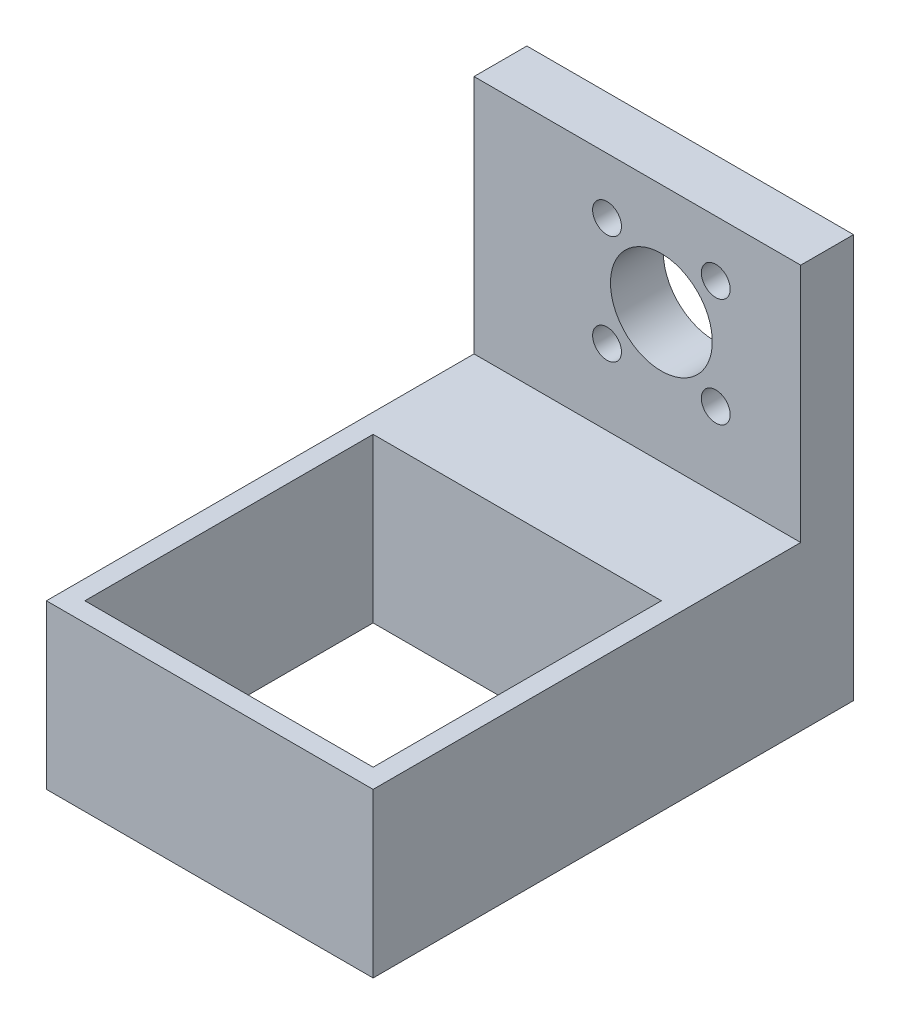
SolidWorks part; units mm, degrees
ref_plane "Płaszczyzna przednia" through (0, 0, 0) normal (0, 0, 1) x (1, 0, 0)
ref_plane "Płaszczyzna górna" through (0, 0, 0) normal (0, 1, 0) x (1, 0, 0)
ref_plane "Płaszczyzna prawa" through (0, 0, 0) normal (1, 0, 0) x (0, 0, -1)
sketch "Szkic1" plane through (0, 0, 0) normal (0, 1, 0) x (1, 0, 0)
  line L1 (-17, 25) -> (17, 25)
  line L2 (-17, 25) -> (-17, -25)
  line L3 (-17, -25) -> (17, -25)
  line L4 (17, 25) -> (17, -25)
  line L5 (-17, 25) -> (17, -25) construction
  line L6 (-17, -25) -> (17, 25) construction
  point P0 (0, 0)
  dimension "D1" = 34
  dimension "D2" = 50
extrude "Dodanie-wyciągnięcie1" add sketch "Szkic1" along normal blind 17
sketch "Szkic2" plane through (0, 17, 0) normal (0, 1, 0) x (1, 0, 0)
  line L0 (0, 25) -> (0, -25) construction
  line L1 (17, 25) -> (-17, 25) construction
  line L2 (-17, -25) -> (17, -25) construction
  line L3 (-17, 25) -> (-17, -25) construction
  line L4 (15, 7) -> (-15, 7)
  line L5 (15, 7) -> (15, -23)
  line L6 (15, -23) -> (-15, -23)
  line L7 (-15, 7) -> (-15, -23)
  line L8 (15, 7) -> (-15, -23) construction
  line L9 (15, -23) -> (-15, 7) construction
  point P6 (0, -8)
  dimension "D1" = 2
  dimension "D2" = 2
  dimension "D3" = 30
extrude "Wytnij-wyciągnięcie1" cut sketch "Szkic2" against normal blind 20
sketch "Szkic3" plane through (0, 17, 0) normal (0, 1, 0) x (1, 0, 0)
  line L0 (17, -25) -> (17, 25) construction
  line L1 (17, 25) -> (-17, 25)
  line L2 (17, 25) -> (17, 19.5)
  line L3 (17, 19.5) -> (-17, 19.5)
  line L4 (-17, 25) -> (-17, 19.5)
  line L5 (17, 25) -> (-17, 25) construction
  line L6 (-17, 25) -> (-17, -25) construction
  line L7 (-17, -25) -> (17, -25) construction
  dimension "D1" = 44.5
extrude "Dodanie-wyciągnięcie2" add sketch "Szkic3" along normal blind 25
sketch "Szkic4" plane through (0, 0, -25) normal (0, 0, -1) x (-1, 0, 0)
  line L0 (-17, 0) -> (17, 0) construction
  line L1 (-2.5, 30.5) -> (-8.1569, 36.1569) construction
  line L2 (-2.5, 30.5) -> (-2.5, 38.5) construction
  line L3 (-17, 42) -> (17, 42) construction
  circle A0 centre (3.1569, 36.1569) radius 1.5
  circle A1 centre (-2.5, 30.5) radius 5.3
  circle A2 centre (-2.5, 30.5) radius 8
  circle A3 centre (-8.1569, 36.1569) radius 1.5
  circle A4 centre (-2.5, 30.5) radius 8
  circle A5 centre (3.1569, 24.8431) radius 1.5
  circle A6 centre (-2.5, 30.5) radius 8
  circle A7 centre (-8.1569, 24.8431) radius 1.5
  circle A8 centre (-2.5, 30.5) radius 8
  point P4 (0, 0)
  point P5 (0, 0)
  point P21 (-2.5, 30.5)
  dimension "D2" = 11.5
  dimension "D3" = 10.6
  dimension "D4" = 16
  dimension "D5" = 3
  dimension "D6" = 45
  dimension "2,5" = 2.5
  dimension "D7" = 4
extrude "Wytnij-wyciągnięcie2" cut sketch "Szkic4" against normal blind 25 contours A2 A3 | A2 A3 | A2 A0 | A0 A2 | A6 A7 | A6 A7 | A4 A5 | A4 A5 | A1 region at (-3.5886, 36.5886, -25) region at (-2.6893, 35.6893, -25) region at (7.6893, 35.6893, -25) region at (8.5886, 36.5886, -25) region at (-3.5886, 24.4114, -25) region at (-2.6893, 25.3107, -25) region at (7.6893, 25.3107, -25) region at (8.5886, 24.4114, -25) region at (2.5, 30.5, -25)
